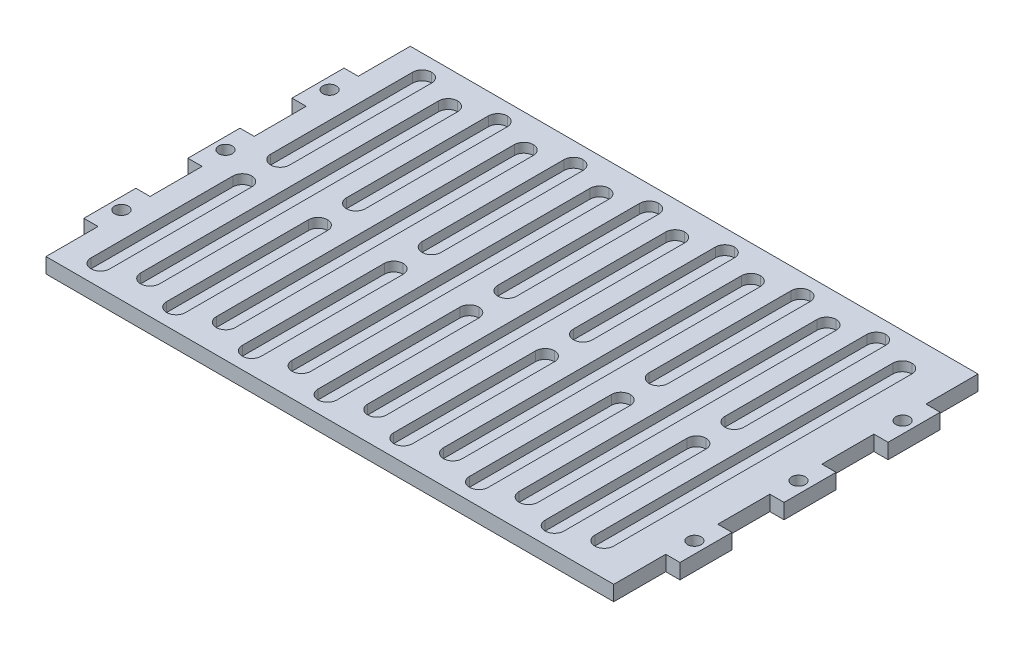
SolidWorks part; units mm, degrees
ref_plane "Front Plane" through (0, 0, 0) normal (0, 0, 1) x (1, 0, 0)
ref_plane "Top Plane" through (0, 0, 0) normal (0, 1, 0) x (1, 0, 0)
ref_plane "Right Plane" through (0, 0, 0) normal (1, 0, 0) x (0, 0, -1)
sketch "Sketch1" plane through (0, 0, 0) normal (0, 1, 0) x (1, 0, 0)
  line L0 (60, 0) -> (-60, 0)
  line L1 (0, -38.5) -> (0, 38.5)
  line L2 (-60, 38.5) -> (60, 38.5)
  line L3 (60, 38.5) -> (60, -38.5)
  line L4 (60, -38.5) -> (-60, -38.5)
  line L5 (-60, -38.5) -> (-60, 38.5)
  point P4 (0, 0)
  point P8 (0, 0)
  dimension "D1" = 0
extrude "Boss-Extrude1" add sketch "Sketch1" along normal blind 3.2 contours L5 L2 L3 L4
sketch "Sketch2" plane through (0, 3.2, 0) normal (0, 1, 0) x (1, 0, 0)
  line L0 (-60, 38.5) -> (-60, 27.5)
  line L1 (-60, -38.5) -> (-60, 38.5) construction
  line L2 (-60, 27.5) -> (-63, 27.5)
  line L3 (-63, 27.5) -> (-63, 16.5)
  line L4 (-63, 16.5) -> (-60, 16.5)
  line L5 (-60, 16.5) -> (-60, 27.5)
extrude "Boss-Extrude2" add sketch "Sketch2" against normal blind 3.2 contours L2 L3 L4 L5
pattern_linear "LPattern1" count 3 spacing 22 along (0, 0, 1) of "Boss-Extrude2"
mirror "Mirror1" about plane through (0, 0, 0) normal (1, 0, 0) of "LPattern1"
sketch "Sketch3" plane through (0, 3.2, 0) normal (0, 1, 0) x (1, 0, 0)
  line L0 (-60, 27.5) -> (-60, 22)
  line L1 (-63, 27.5) -> (-63, 16.5) construction
  circle A0 centre (-60.56, 22) radius 1.44
  dimension "D1" = 2.44
extrude "Cut-Extrude1" cut sketch "Sketch3" against normal through all contours A0 region at (-60.56, 3.2, -22)
pattern_linear "LPattern2" count 3 spacing 22 along (0, 0, 1) of "Cut-Extrude1"
mirror "Mirror2" about plane through (0, 0, 0) normal (1, 0, 0) of "LPattern2", "Cut-Extrude1"
sketch "Sketch4" plane through (0, 3.2, 0) normal (0, 1, 0) x (1, 0, 0)
  line L0 (-60, 38.5) -> (-55, 38.5)
  line L1 (-60, 38.5) -> (60, 38.5) construction
  line L2 (-55, 38.5) -> (-55, 36)
  line L3 (-55, 36) -> (-51, 36)
  line L4 (-51, 36) -> (-51, 2)
  line L5 (-51, 2) -> (-55, 2)
  line L6 (-55, 2) -> (-55, 36)
  line L7 (-55, 2) -> (-55, -2)
  line L8 (-55, -2) -> (-51, -2)
  line L9 (-51, -2) -> (-51, -36)
  line L10 (-51, -36) -> (-55, -36)
  line L11 (-55, -36) -> (-55, -2)
  line L12 (-51, -36) -> (-51, -38.5)
  line L13 (60, -38.5) -> (-60, -38.5) construction
  line L14 (-51, -38.5) -> (-47, -38.5)
  line L15 (-47, -38.5) -> (-47, -33.5)
  line L16 (-47, -33.5) -> (-43, -33.5)
  line L17 (-43, -33.5) -> (-43, 33.5)
  line L18 (-43, 33.5) -> (-47, 33.5)
  line L19 (-47, 33.5) -> (-47, -33.5)
  line L20 (-47, 33.5) -> (-47, 38.5)
extrude "Cut-Extrude2" cut sketch "Sketch4" against normal blind 2 contours L6 L5 L4 L3 | L18 L19 L16 L17 | L11 L10 L9 L8 region at (-45, 3.2, 0) region at (-53, 3.2, 19) region at (-53, 3.2, -19)
fillet "Fillet1" radius 2 12 edges at (-47, 2.2, -33.5) (-55, 2.2, -36) (-51, 2.2, -36) (-43, 2.2, -33.5) (-55, 2.2, -2) (-51, 2.2, -2) (-55, 2.2, 2) (-51, 2.2, 2) (-51, 2.2, 36) (-55, 2.2, 36) (-47, 2.2, 33.5) (-43, 2.2, 33.5)
pattern_linear "LPattern3" count 7 spacing 16 along (1, 0, 0) of "Cut-Extrude2", "Fillet1"
